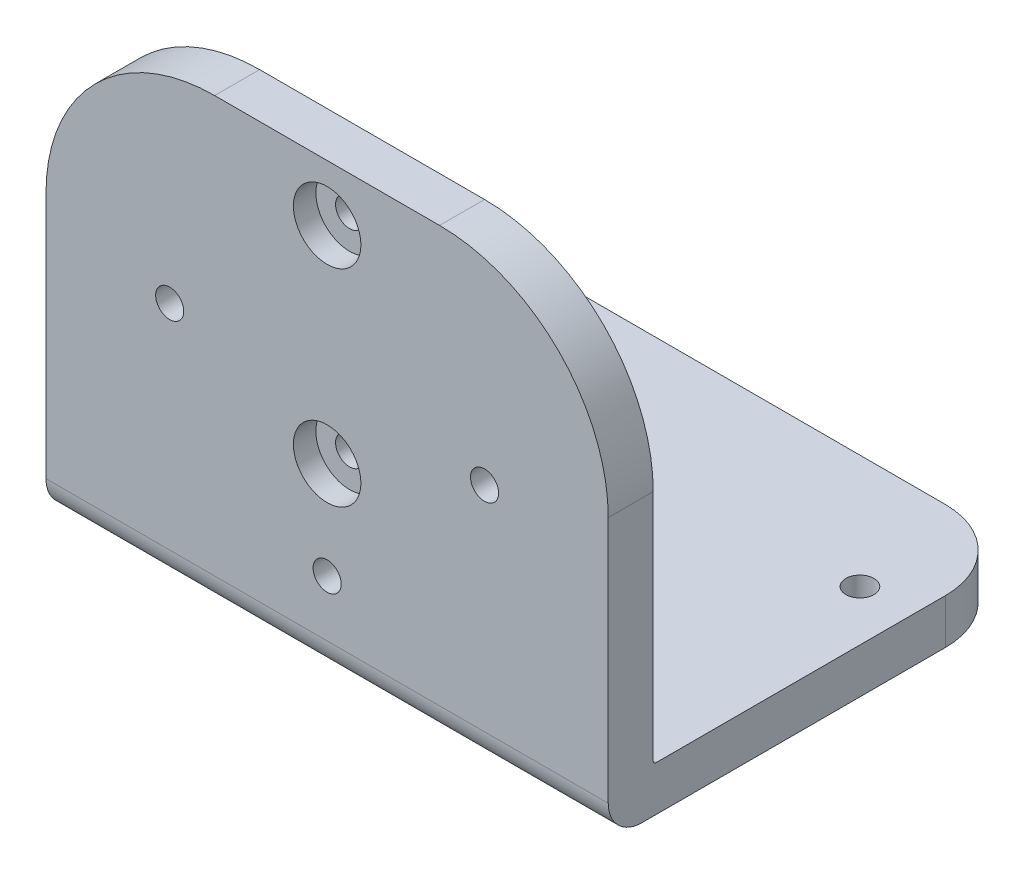
SolidWorks part; units mm, degrees
material "AISI 304"
ref_plane "Plano frontal" through (0, 0, 0) normal (0, 0, 1) x (1, 0, 0)
ref_plane "Plano superior" through (0, 0, 0) normal (0, 1, 0) x (1, 0, 0)
ref_plane "Plano direito" through (0, 0, 0) normal (1, 0, 0) x (0, 0, -1)
sketch "Esboço1" plane through (0, 0, 0) normal (1, 0, 0) x (0, 0, -1)
  line L0 (0, 0) -> (37, 0)
  line L1 (0, 0) -> (0, 40)
  line L2 (0, 40) -> (4, 40)
  line L3 (4, 40) -> (4, 4)
  line L4 (4, 4) -> (37, 4)
  line L5 (37, 4) -> (37, 0)
  dimension "D1" = 4
  dimension "D2" = 37
  dimension "D3" = 40
extrude "Ressalto-extrusão1" add sketch "Esboço1" along normal mid plane 50
sketch "Esboço2" plane through (0, 4, 0) normal (0, 1, 0) x (1, 0, 0)
  line L0 (0, 58.5094) -> (0, -20.9701) construction
  line L1 (25, 37) -> (-25, 37) construction
  line L2 (-25, 37) -> (-25, 4) construction
  line L3 (25, 37) -> (25, 4) construction
  circle A0 centre (20.5, 26.88) radius 3
  circle A1 centre (-15.5, 26.88) radius 3
  circle A2 centre (-15.5, 26.88) radius 1.25
  circle A3 centre (20.5, 26.88) radius 1.25
  dimension "D1" = 6
  dimension "D2" = 6
  dimension "D3" = 2.5
  dimension "D4" = 10.12
  dimension "D5" = 9.5
  dimension "D6" = 4.5
  dimension "D7" = 10.12
extrude "Corte-extrusão1" cut sketch "Esboço2" along normal offset from surface (2 mm away) 2 from surface up to face at (0, 4, -20.5) starting at face at (0, 0, -18.5)
extrude "Corte-extrusão2" cut sketch "Esboço2<5>" against normal through all contours A2 region at (-15.5, 4, -26.88)
sketch "Esboço2<5>" plane through (0, 4, 0) normal (0, 1, 0) x (1, 0, 0) same geometry as "Esboço2"
extrude "Corte-extrusão3" cut sketch "Esboço2<6>" against normal through all contours A3 region at (20.5, 4, -26.88)
sketch "Esboço2<6>" plane through (0, 4, 0) normal (0, 1, 0) x (1, 0, 0) same geometry as "Esboço2"
sketch "Esboço4" plane through (0, 0, -4) normal (0, 0, -1) x (-1, 0, 0)
  line L0 (0, 60.7566) -> (0, -21.371) construction
  line L1 (-25, 0) -> (25, 0) construction
  line L2 (-25, 4) -> (-25, 40) construction
  line L3 (-25, 40) -> (25, 40) construction
  circle A0 centre (14, 22) radius 3
  circle A1 centre (-14, 22) radius 3
  circle A2 centre (-14, 22) radius 1.25
  circle A3 centre (14, 22) radius 1.25
  circle A4 centre (0, 8) radius 3
  circle A5 centre (0, 8) radius 1.25
  circle A6 centre (0, 35) radius 3
  circle A7 centre (0, 35) radius 1.25
  circle A8 centre (0, 16.65) radius 3
  circle A9 centre (0, 16.65) radius 1.25
  dimension "D1" = 6
  dimension "D2" = 22
  dimension "D3" = 11
  dimension "D4" = 2.5
  dimension "D5" = 6
  dimension "D6" = 2.5
  dimension "D7" = 8
  dimension "D8" = 6
  dimension "D9" = 2.5
  dimension "D10" = 5
  dimension "D11" = 23.35
  dimension "D12" = 2.5
extrude "Corte-extrusão4" cut sketch "Esboço4" against normal blind 2 contours A0 A3 | A1 A2 | L0 A4 A5 | A4 L0 A5 region at (-1.4293, 8, -4) region at (1.4293, 8, -4) region at (-11.0849, 22, -4) region at (16.9151, 22, -4)
extrude "Corte-extrusão5" cut sketch "Esboço4<4>" against normal through all contours A2 | A3 | A5 L0 | L0 A5 region at (-0.5305, 8, -4) region at (0.5305, 8, -4) region at (14, 22, -4) region at (-14, 22, -4)
sketch "Esboço4<4>" plane through (0, 0, -4) normal (0, 0, -1) x (-1, 0, 0) same geometry as "Esboço4"
extrude "Corte-extrusão8" cut sketch "Esboço4<11>" along normal blind 2 from surface contours A8 L0 A9 | L0 A8 A9 | A6 L0 A7 | L0 A6 A7 region at (-1.4293, 35, -4) region at (-1.4293, 16.65, -4) region at (1.4293, 16.65, -4) region at (1.4293, 35, -4) starting at face at (14, 23.25, 0)
sketch "Esboço4<11>" plane through (0, 0, -4) normal (0, 0, -1) x (-1, 0, 0) same geometry as "Esboço4"
extrude "Corte-extrusão9" cut sketch "Esboço4<12>" against normal through all contours A7 L0 | L0 A7 | A9 L0 | L0 A9 region at (-0.5305, 35, -4) region at (0.5305, 35, -4) region at (-0.5305, 16.65, -4) region at (0.5305, 16.65, -4)
sketch "Esboço4<12>" plane through (0, 0, -4) normal (0, 0, -1) x (-1, 0, 0) same geometry as "Esboço4"
fillet "Filete1" radius 15 2 edges at (25, 40, -2) (-25, 40, -2)
fillet "Filete2" radius 7 2 edges at (-25, 2, -37) (25, 2, -37)
fillet "Filete3" radius 0.25 1 edges at (0, 4, -4)
fillet "Filete4" radius 3 1 edges at (0, 0, 0)
